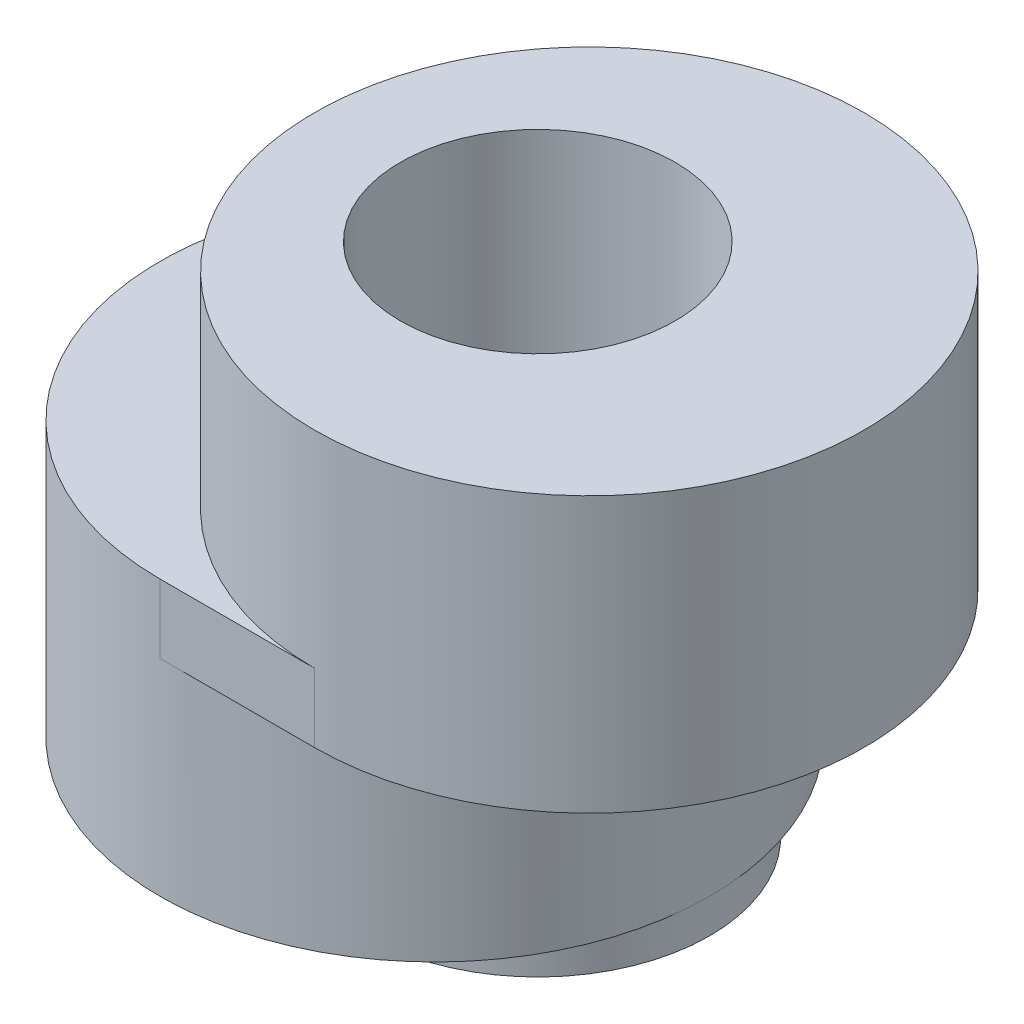
SolidWorks part; units mm, degrees
ref_plane "前视基准面" through (0, 0, 0) normal (0, 0, 1) x (1, 0, 0)
ref_plane "上视基准面" through (0, 0, 0) normal (0, 1, 0) x (1, 0, 0)
ref_plane "右视基准面" through (0, 0, 0) normal (1, 0, 0) x (0, 0, -1)
sketch "草图1" plane through (0, 0, 0) normal (0, 1, 0) x (1, 0, 0)
  line L0 (0, 0) -> (-1.5, 0) construction
  circle A0 centre (0, 0) radius 2
  circle A1 centre (-1.5, 0) radius 4
  dimension "D1" = 1.5
  dimension "D2" = 4
  dimension "D3" = 8
extrude "凸台-拉伸1" add sketch "草图1" along normal blind 3
sketch "草图2" plane through (0, 3, 0) normal (0, 1, 0) x (1, 0, 0)
  line L0 (-1.5, 4) -> (0.75, 4)
  line L1 (-1.5, -4) -> (0.75, -4)
  circle A0 centre (0, 0) radius 2 construction
  circle A1 centre (0, 0) radius 2
  arc A2 (0.75, -4) -> (0.75, 4) centre (0.75, 0) ccw
  circle A3 centre (-1.5, 0) radius 4 construction
  arc A4 (-1.5, 4) -> (-1.5, -4) centre (-1.5, 0) ccw
  dimension "D1" = 0.75
extrude "凸台-拉伸2" add sketch "草图2" along normal blind 1
sketch "草图3" plane through (0, 4, 0) normal (0, 1, 0) x (1, 0, 0)
  circle A0 centre (0.75, 0) radius 4
  circle A1 centre (0, 0) radius 2 construction
  circle A2 centre (0, 0) radius 2
extrude "凸台-拉伸3" add sketch "草图3" along normal blind 3
sketch "草图4" plane through (0, 0, 0) normal (0, -1, 0) x (1, 0, 0)
  circle A0 centre (0, 0) radius 2.5
  circle A1 centre (0, 0) radius 2 construction
  circle A2 centre (0, 0) radius 2
  circle A3 centre (-1.5, 0) radius 4 construction
extrude "凸台-拉伸4" add sketch "草图4" along normal blind 0.5
